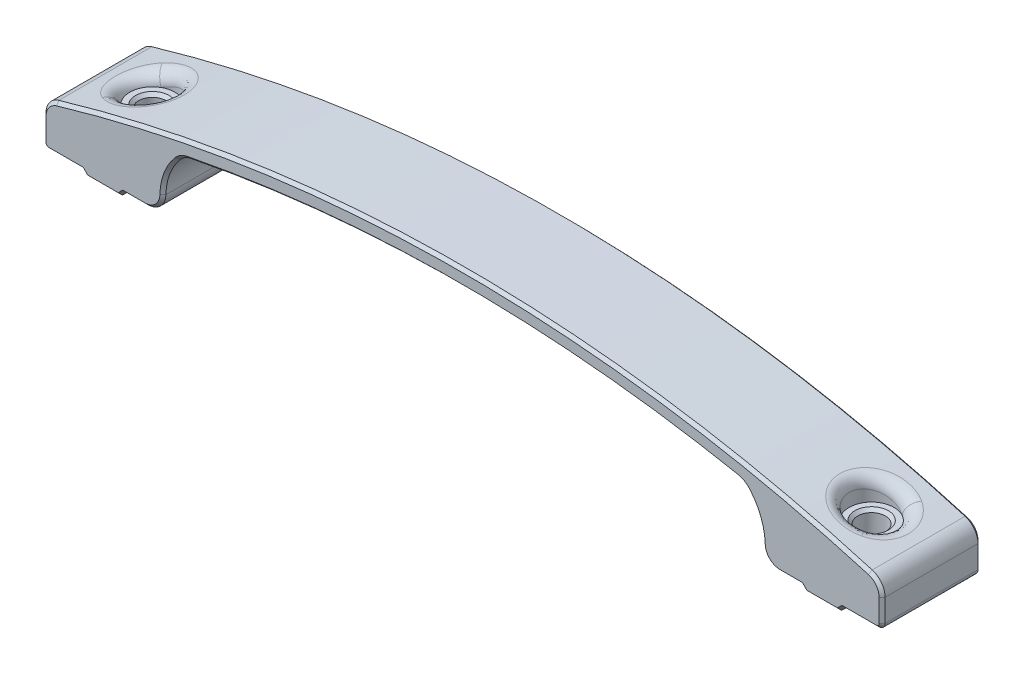
SolidWorks part; units mm, degrees
ref_plane "Front" through (0, 0, 0) normal (0, 0, 1) x (1, 0, 0)
ref_plane "Top" through (0, 0, 0) normal (0, 1, 0) x (1, 0, 0)
ref_plane "Right" through (0, 0, 0) normal (1, 0, 0) x (0, 0, -1)
sketch "Skizze1" plane through (0, 0, 0) normal (0, 0, 1) x (1, 0, 0)
  line L0 (-70, 0) -> (70, 0) construction
  line L1 (70, 0) -> (70, 7)
  line L3 (50, 2.7103) -> (50, 0)
  line L4 (50, 0) -> (70, 0)
  line L5 (0, 0) -> (0, 27.6946) construction
  line L12 (-50, 0) -> (-70, 0)
  line L13 (-50, 2.7103) -> (-50, 0)
  line L15 (-70, 0) -> (-70, 7)
  arc A7 (70, 7) -> (-70, 7) centre (0, -222.6075) ccw
  arc A8 (40.7458, 13.9441) -> (-40.7769, 13.9441) centre (-0.0155, -222.5565) ccw construction
  arc A9 (-41.7479, 12.5564) -> (41.7479, 12.5564) centre (0, -222.6075) cw
  arc A10 (-50, 2.7103) -> (-41.7479, 12.5564) centre (-40, 2.7103) cw
  arc A11 (41.7479, 12.5564) -> (50, 2.7103) centre (40, 2.7103) cw
  point P12 (-50, 10.9411)
  point P20 (50, 10.9411)
  dimension "D4" = 1.2
  dimension "D5" = 10
  dimension "D1" = 20
  dimension "D2" = 7
  dimension "D3" = 140
extrude "Aufsatz-Linear austragen1" add sketch "Skizze1" along normal blind 16.5
sketch "Skizze2" plane through (0, 0, 16.5) normal (0, 0, 1) x (1, 0, 0)
  line L0 (50, 0) -> (-50, 0)
  line L6 (50, 0) -> (70, 0)
  line L7 (70, 0) -> (70, 7)
  line L8 (-70, 7) -> (-70, 0)
  line L9 (-70, 0) -> (-50, 0)
  line L10 (-50, 0) -> (-50, 2.7103)
  line L11 (50, 2.7103) -> (50, 0)
  line L12 (50, 0) -> (70, 0)
  line L13 (70, 0) -> (70, 7)
  line L14 (-70, 7) -> (-70, 0)
  line L15 (-70, 0) -> (-50, 0)
  arc A4 (70, 7) -> (-70, 7) centre (0, -222.6075) ccw
  arc A5 (-41.7479, 12.5564) -> (-50, 2.7103) centre (-40, 2.7103) ccw
  arc A6 (41.7479, 12.5564) -> (-41.7479, 12.5564) centre (0, -222.6075) ccw
  arc A7 (50, 2.7103) -> (41.7479, 12.5564) centre (40, 2.7103) ccw
  arc A8 (70, 7) -> (-70, 7) centre (0, -222.6075) ccw
  dimension "D1" = 0
extrude "Aufsatz-Linear austragen2" [suppressed] add sketch "Skizze2" against normal blind 1
sketch "Skizze8" plane through (0, 0, 0) normal (0, 0, -1) x (-1, 0, 0)
  line L0 (-60, 0) -> (-60, -10.9272) construction
  line L1 (-50, 0) -> (-70, 0) construction
  line L2 (-63.5, 0) -> (-56.5, 0)
  line L3 (-56.5, 0) -> (-57.25, -0.75)
  line L4 (-57.25, -0.75) -> (-62.75, -0.75)
  line L5 (-63.5, 0) -> (-62.75, -0.75)
  line L6 (0, 0) -> (0, -16.4832) construction
  line L7 (56.5, 0) -> (57.25, -0.75)
  line L8 (63.5, 0) -> (56.5, 0)
  line L9 (63.5, 0) -> (62.75, -0.75)
  line L10 (57.25, -0.75) -> (62.75, -0.75)
  point P9 (-60, -0.75)
  dimension "D1" = 0.75
  dimension "D2" = 7
  dimension "D3" = 45
extrude "Aufsatz-Linear austragen7" add sketch "Skizze8" against normal up to surface (16.5 mm away) up to face at (0, 6.1645, 16.5)
sketch "Skizze3" plane through (0, 0, 0) normal (0, -1, 0) x (1, 0, 0)
  line L0 (-60, 0) -> (-60, 16.5) construction
  line L2 (-70, 16.5) -> (-63.5, 16.5) construction
  line L3 (-57.25, 0) -> (-62.75, 0) construction
  line L5 (0, 0) -> (0, 46.7735) construction
  line L6 (-41.7479, 0) -> (41.7479, 0) construction
  circle A0 centre (-60, 8.25) radius 2.3
  circle A1 centre (-60, 8.25) radius 3.75
  circle A2 centre (60, 8.25) radius 3.75
  circle A3 centre (60, 8.25) radius 2.3
  point P2 (-60, 0)
  point P16 (0, 0)
  dimension "D1" = 4.6
  dimension "D2" = 7.5
extrude "Schnitt-Linear austragen1" cut sketch "Skizze3" against normal through all and the other way blind 10 contours A0 | A3 region at (-60, 0, 8.25) region at (60, 0, 8.25)
extrude "Schnitt-Linear austragen2" cut sketch "Skizze3<3>" against normal through all from offset 7 offset against normal yes
sketch "Skizze3<3>" plane through (0, 0, 0) normal (0, -1, 0) x (1, 0, 0) same geometry as "Skizze3"
sketch "Skizze7" plane through (0, 0, 0) normal (0, 0, -1) x (-1, 0, 0)
  line L0 (0, 0) -> (0, 25.3152) construction
  line L1 (-2.5, 14.7333) -> (2.5, 14.7333)
  line L2 (2.5, 14.7333) -> (2.5, 16.2203)
  line L3 (2.5, 16.2203) -> (0, 16.7935)
  line L4 (-2.5, 16.2203) -> (0, 16.7935)
  line L5 (-2.5, 14.7333) -> (-2.5, 16.2203)
  arc A0 (41.7479, 12.5564) -> (-41.7479, 12.5564) centre (0, -222.6075) ccw construction
  point P5 (0, 16.2333)
  point P13 (0, 14.7333)
  dimension "D1" = 5
  dimension "D2" = 1.5
extrude "Aufsatz-Linear austragen6" add sketch "Skizze7" against normal up to surface (16.5 mm away) up to face at (0, 3.258, 16.5)
sketch "Skizze6" plane through (0, 0, 0) normal (0, 0, -1) x (-1, 0, 0)
  line L6 (50, 0) -> (56.5, 0)
  line L7 (-50, 0) -> (-50, 2.7103)
  line L8 (50, 2.7103) -> (50, 0)
  line L9 (-56.5, 0) -> (-50, 0)
  line L10 (70, 0) -> (70, 7)
  line L11 (-70, 7) -> (-70, 0)
  line L13 (-56.5, 0) -> (-50, 0)
  line L17 (-2.5, 16.2203) -> (-2.5, 14.7333)
  line L18 (-2.5, 16.2203) -> (-2.5, 14.7333)
  line L19 (-2.5, 14.7333) -> (2.5, 14.7333)
  line L20 (-2.5, 14.7333) -> (2.5, 14.7333)
  line L21 (2.5, 14.7333) -> (2.5, 16.2203)
  line L22 (2.5, 14.7333) -> (2.5, 16.2203)
  line L34 (56.5, 0) -> (57.25, -0.75)
  line L35 (56.5, 0) -> (57.25, -0.75)
  line L36 (57.25, -0.75) -> (62.75, -0.75)
  line L37 (57.25, -0.75) -> (62.75, -0.75)
  line L38 (62.75, -0.75) -> (63.5, 0)
  line L39 (62.75, -0.75) -> (63.5, 0)
  line L40 (63.5, 0) -> (70, 0)
  line L41 (63.5, 0) -> (70, 0)
  line L42 (-70, 0) -> (-63.5, 0)
  line L43 (-70, 0) -> (-63.5, 0)
  line L44 (-63.5, 0) -> (-62.75, -0.75)
  line L45 (-63.5, 0) -> (-62.75, -0.75)
  line L46 (-62.75, -0.75) -> (-57.25, -0.75)
  line L47 (-62.75, -0.75) -> (-57.25, -0.75)
  line L48 (-57.25, -0.75) -> (-56.5, 0)
  line L49 (-57.25, -0.75) -> (-56.5, 0)
  arc A0 (-46.757, 10.0821) -> (46.757, 10.0821) centre (0, -222.6075) cw
  arc A4 (-41.7479, 12.5564) -> (-50, 2.7103) centre (-40, 2.7103) ccw
  arc A5 (-2.5, 16.2203) -> (-41.7479, 12.5564) centre (0, -222.6075) ccw
  arc A6 (50, 2.7103) -> (41.7479, 12.5564) centre (40, 2.7103) ccw
  arc A7 (70, 7) -> (-70, 7) centre (0, -222.6075) ccw
  arc A8 (-41.7479, 12.5564) -> (-46.757, 10.0821) centre (-40, 2.7103) ccw
  arc A9 (-2.5, 16.2203) -> (-41.7479, 12.5564) centre (0, -222.6075) ccw
  arc A10 (46.757, 10.0821) -> (41.7479, 12.5564) centre (40, 2.7103) ccw
  arc A14 (41.7479, 12.5564) -> (2.5, 16.2203) centre (0, -222.6075) ccw
  arc A15 (41.7479, 12.5564) -> (2.5, 16.2203) centre (0, -222.6075) ccw
  arc M14 (-50, 2.7103) -> (-41.7479, 12.5564) centre (-40, 2.7103) cw
  arc M15 (-41.7479, 12.5564) -> (-2.5, 16.2203) centre (0, -222.6075) cw
  arc M16 (41.7479, 12.5564) -> (50, 2.7103) centre (40, 2.7103) cw
  line M38 (2.5, 14.7333) -> (2.5, 16.2203)
  arc M39 (2.5, 16.2203) -> (41.7479, 12.5564) centre (0, -222.6075) cw
  dimension "D2" = 1.5
  dimension "D1" = 0
extrude "Aufsatz-Linear austragen4" add sketch "Skizze6" against normal blind 2 contours A0 M14 M16 M15 | L20 A0 M16 M39 M38 region at (-23.9242, 13.9402, 0) region at (23.9242, 13.9402, 0)
extrude "Aufsatz-Linear austragen5" add sketch "Skizze6<3>" along normal blind 2 from surface contours A0 M14 M16 M15 | L20 A0 M16 M39 M38 region at (-23.9242, 13.9402, 0) region at (23.9242, 13.9402, 0) starting at face at (0, 5.3862, 16.5)
sketch "Skizze6<3>" plane through (0, 0, 0) normal (0, 0, -1) x (-1, 0, 0) same geometry as "Skizze6"
sketch "Skizze4" [suppressed] plane through (0, 0, 15.5) normal (0, 0, -1) x (-1, 0, 0)
  line L0 (0, 0) -> (0, 24.1531) construction
  line L1 (-2.5, 14.7333) -> (2.5, 14.7333)
  line L2 (2.5, 14.7333) -> (2.5, 16.2203)
  line L3 (2.5, 16.2203) -> (0, 16.737)
  line L4 (-2.5, 16.2203) -> (0, 16.737)
  line L5 (-2.5, 14.7333) -> (-2.5, 16.2203)
  arc A0 (-41.7479, 12.5564) -> (41.7479, 12.5564) centre (0, -222.6075) ccw construction
  point P5 (0, 16.2333)
  point P13 (0, 14.7333)
  dimension "D1" = 5
  dimension "D2" = 1.5
extrude "Aufsatz-Linear austragen3" [suppressed] add sketch "Skizze4" along normal up to surface (15.5 mm away) up to face at (0, 2.9084, 0)
sketch "Skizze9" plane through (0, 0, 0) normal (0, -1, 0) x (1, 0, 0)
  circle A0 centre (-60, 8.25) radius 4.15
  circle A1 centre (60, 8.25) radius 4.15
  dimension "D1" = 8.3
extrude "Schnitt-Linear austragen3" cut sketch "Skizze9" along normal blind 10
fillet "Verrundung1" radius 3 8 edges at (-50, 0, 8.25) (-70, 7, 8.25) (70, 7, 8.25) (46.757, 10.0821, 1) (-46.757, 10.0821, 1) (-46.757, 10.0821, 15.5) (50, 0, 8.25) (46.757, 10.0821, 15.5)
fillet "Verrundung2" radius 1 2 edges at (-70, 0, 8.25) (70, 0, 8.25)
chamfer "Fase1" [suppressed] distance 3 angle 45
chamfer "Fase3" distance 1.5 angle 45 8 edges at (44.9155, 11.4188, 14.5) (22.1997, 15.1994, 14.5) (-44.9155, 11.4188, 14.5) (-22.1997, 15.1994, 14.5) (-44.9155, 11.4188, 2) (-22.1997, 15.1994, 2) (44.9155, 11.4188, 2) (22.1997, 15.1994, 2)
chamfer "Fase2" distance 0.5 angle 45 52 edges at (-50.8992, 0.8552, 0) (-49.3214, 6.3313, 0) (49.3214, 6.3313, 0) (70, 2.8837, 0) (69.4025, 6.5641, 0) (0, 17.4333, 0) (-69.4025, 6.5641, 0) (-70, 2.8837, 0) (-69.7071, 0.2929, 0) (-66.25, 0, 0) (-54.7484, 0, 0) (-69.4025, 6.5641, 16.5) (0, 17.4333, 16.5) (69.4025, 6.5641, 16.5) (70, 2.8837, 16.5) (-66.25, 0, 16.5) (-69.7071, 0.2929, 16.5) (-70, 2.8837, 16.5) (-60, 7, 5.95) (60, 7, 10.55) (60, 0, 5.95) (-46.7674, 9.9181, 0) (46.7674, 9.9181, 0) (-60, 0, 5.95) (49.3214, 6.3313, 16.5) (-49.3214, 6.3313, 16.5) (-50.8992, 0.8552, 16.5) (0, 14.7333, 0) (0, 14.7333, 16.5) (50.8992, 0.8552, 0) (50.8992, 0.8552, 16.5) (46.7674, 9.9181, 16.5) (-46.7674, 9.9181, 16.5) (69.7071, 0.2929, 0) (69.7071, 0.2929, 16.5) (-63.125, -0.375, 0) (-60, -0.75, 0) (-56.875, -0.375, 0) (54.7484, 0, 0) (56.875, -0.375, 0) (60, -0.75, 0) (63.125, -0.375, 0) (66.25, 0, 0) (63.125, -0.375, 16.5) (60, -0.75, 16.5) (56.875, -0.375, 16.5) (54.7484, 0, 16.5) (-54.7484, 0, 16.5) (-56.875, -0.375, 16.5) (-60, -0.75, 16.5) (-63.125, -0.375, 16.5) (66.25, 0, 16.5)
fillet "Verrundung3" radius 2 2 edges at (59.116, 10.0401, 11.8943) (-60.8742, 9.5863, 11.8967)
fillet "Verrundung4" radius 0.73 4 edges at (-2.5, 14.7333, 8.25) (-2.5, 16.2203, 8.25) (2.5, 16.2203, 8.25) (2.5, 14.7333, 8.25)
fillet "Verrundung5" radius 0.75 4 edges at (60, -0.75, 12.4) (60, -0.75, 4.1) (-60, -0.75, 12.4) (-60, -0.75, 4.1)
